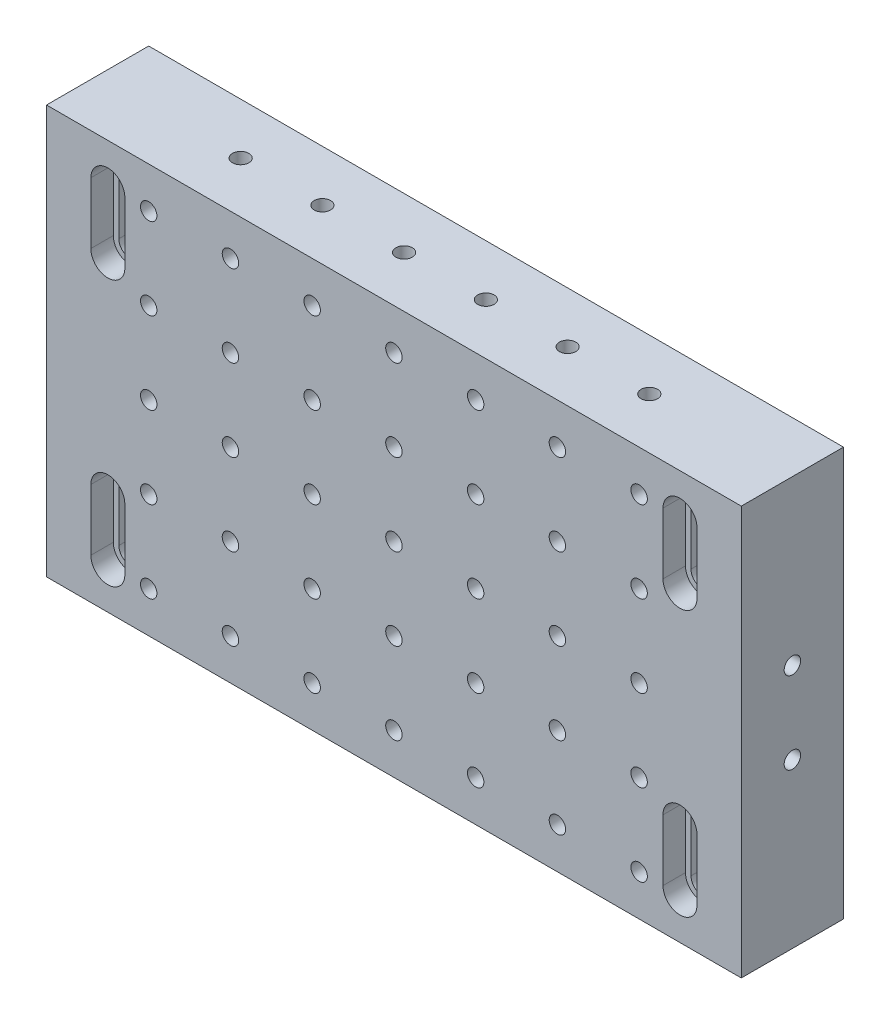
SolidWorks part; units mm, degrees
ref_plane "Front Plane" through (0, 0, 0) normal (0, 0, 1) x (1, 0, 0)
ref_plane "Top Plane" through (0, 0, 0) normal (0, 1, 0) x (1, 0, 0)
ref_plane "Right Plane" through (0, 0, 0) normal (1, 0, 0) x (0, 0, -1)
sketch "Sketch1" plane through (0, 0, 0) normal (0, 0, 1) x (1, 0, 0)
  line L1 (0, 0) -> (215.9, 0)
  line L2 (0, 0) -> (0, 127)
  line L3 (0, 127) -> (215.9, 127)
  line L4 (215.9, 0) -> (215.9, 127)
  dimension "D1" = 215.9
  dimension "D2" = 127
extrude "Boss-Extrude1" add sketch "Sketch1" along normal blind 31.75
sketch "Sketch2" plane through (0, 0, 0) normal (0, -1, 0) x (1, 0, 0)
  line L0 (13.7668, 31.75) -> (13.7668, 24.765)
  line L1 (0, 31.75) -> (215.9, 31.75) construction
  line L2 (13.7668, 24.765) -> (15.4813, 24.765)
  line L3 (15.4813, 24.765) -> (15.4813, 0)
  line L4 (0, 0) -> (215.9, 0) construction
  line L5 (15.4813, 0) -> (22.6187, 0)
  line L6 (22.6187, 0) -> (22.6187, 24.765)
  line L7 (22.6187, 24.765) -> (24.3332, 24.765)
  line L8 (24.3332, 24.765) -> (24.3332, 31.75)
  line L9 (24.3332, 31.75) -> (13.7668, 31.75)
  line L10 (19.05, 0) -> (19.05, 31.75) construction
extrude "Cut-Extrude1" cut sketch "Sketch2" against normal blind 19.05 from offset 12.7 offset against normal yes
sketch "Sketch4" plane through (0, 31.75, 0) normal (0, -1, 0) x (1, 0, 0)
  line L0 (19.05, 0) -> (19.05, 31.75)
  line L1 (15.4813, 0) -> (22.6187, 0) construction
  line L2 (24.3332, 31.75) -> (13.7668, 31.75) construction
  line L3 (19.05, 31.75) -> (13.7668, 31.75)
  line L4 (13.7668, 31.75) -> (13.7668, 24.765)
  line L5 (13.7668, 24.765) -> (15.4813, 24.765)
  line L6 (15.4813, 24.765) -> (15.4813, 0)
  line L7 (15.4813, 0) -> (19.05, 0)
revolve "Cut-Revolve3" cut sketch "Sketch4" angle 360 about L0
sketch "Sketch6" plane through (0, 12.7, 0) normal (0, 1, 0) x (1, 0, 0)
  line L0 (19.05, 0) -> (19.05, -31.75)
  line L1 (15.4813, 0) -> (22.6187, 0) construction
  line L2 (24.3332, -31.75) -> (13.7668, -31.75) construction
  line L3 (19.05, -31.75) -> (24.3332, -31.75)
  line L4 (24.3332, -31.75) -> (24.3332, -24.765)
  line L5 (24.3332, -24.765) -> (22.6187, -24.765)
  line L6 (22.6187, -24.765) -> (22.6187, 0)
  line L7 (22.6187, 0) -> (19.05, 0)
revolve "Cut-Revolve4" cut sketch "Sketch6" angle 360 about L0
pattern_linear "LPattern1" count 2 spacing 82.55 along (0, 1, 0) count 2 spacing 177.8 along (1, 0, 0) of "Cut-Extrude1", "Cut-Revolve3", "Cut-Revolve4"
hole_wizard "1/4-20 Tapped Hole1" positions "Sketch8" profile "Sketch7" tap size "1/4-20" standard "Ansi Inch" end condition through all
sketch "Sketch8" plane through (0, 0, 31.75) normal (0, 0, 1) x (1, 0, 0)
  line L1 (0, 0) -> (215.9, 0) construction
  line L2 (0, 127) -> (0, 0) construction
  point P0 (31.75, 12.7)
  dimension "D1" = 31.75
  dimension "D2" = 12.7
sketch "Sketch7" plane through (31.75, 12.7, 31.75) normal (1, 0, 0) x (0, -1, 0)
  line L0 (0, 0) -> (0, 31.75)
  line L1 (0, 31.75) -> (2.5527, 31.75)
  line L2 (2.5527, 31.75) -> (2.5527, 0)
  line L5 (2.5527, 0) -> (0, 0)
  line L11 (0, -6.35) -> (0, 107.95) construction
  dimension "Thru Tap Drill Dia." = 5.1054
  dimension "Thru Tap Drill Depth" = 31.75
cosmetic thread "Hole Thread10" parameters "D2"=6.35
hole_wizard "1/4-20 Tapped Hole3" positions "Sketch12" profile "Sketch14" tap size "1/4-20" standard "Ansi Inch"
sketch "Sketch12" plane through (215.9, -229.0211, 31.4791) normal (1, 0, 0) x (0, 0, -1)
  line L2 (-0.2709, 229.0211) -> (-0.2709, 356.0211) construction
  line L3 (-0.2709, 229.0211) -> (31.4791, 229.0211) construction
  point P0 (15.6041, 279.8211)
  dimension "D1" = 15.875
  dimension "D2" = 50.8
sketch "Sketch14" plane through (215.9, 50.8, 15.875) normal (0, 1, 0) x (0, 0, -1)
  line L0 (0, 0) -> (0, 33.2838)
  line L1 (0, 33.2838) -> (2.5527, 31.75)
  line L2 (2.5527, 31.75) -> (2.5527, 0)
  line L5 (2.5527, 0) -> (0, 0)
  line L10 (0, 33.2838) -> (-2.5527, 31.75) construction
  line L11 (0, -6.35) -> (0, 107.95) construction
  dimension "Tap Drill Dia." = 5.1054
  dimension "Tap Drill Depth" = 31.75
  dimension "Drill Angle" = 118
cosmetic thread "Hole Thread3" parameters "D1"=25.4, "D2"=6.35
hole_wizard "1/4-20 Tapped Hole5" positions "Sketch20" profile "Sketch22" tap size "1/4-20" standard "Ansi Inch"
sketch "Sketch20" plane through (169.6356, 127, -274.3412) normal (0, 1, 0) x (-1, 0, 0)
  line L2 (-46.2644, 306.0912) -> (169.6356, 306.0912) construction
  line L3 (-46.2644, 306.0912) -> (-46.2644, 274.3412) construction
  point P0 (-1.8144, 290.2162)
  dimension "D1" = 15.875
  dimension "D2" = 44.45
sketch "Sketch22" plane through (171.45, 127, 15.875) normal (1, 0, 0) x (0, 0, 1)
  line L0 (0, 0) -> (0, 33.2838)
  line L1 (0, 33.2838) -> (2.5527, 31.75)
  line L2 (2.5527, 31.75) -> (2.5527, 0)
  line L5 (2.5527, 0) -> (0, 0)
  line L10 (0, 33.2838) -> (-2.5527, 31.75) construction
  line L11 (0, -6.35) -> (0, 107.95) construction
  dimension "Tap Drill Dia." = 5.1054
  dimension "Tap Drill Depth" = 31.75
  dimension "Drill Angle" = 118
cosmetic thread "Hole Thread7" parameters "D1"=25.4, "D2"=6.35
pattern_linear "LPattern7" count 6 spacing 25.4 along (-1, 0, 0) of "1/4-20 Tapped Hole5"
ref_plane "centerplane1" through (107.95, 0, 0) normal (1, 0, 0) x (0, 0, -1)
ref_plane "centerplane2" through (0, 63.5, 0) normal (0, 1, 0) x (-1, 0, 0)
pattern_linear "LPattern10" count 7 spacing 25.4 along (1, 0, 0) count 5 spacing 25.4 along (0, 1, 0) of "1/4-20 Tapped Hole1"
mirror "Mirror1" about plane through (107.95, 0, 0) normal (1, 0, 0) of "1/4-20 Tapped Hole3"
mirror "Mirror2" about plane through (0, 63.5, 0) normal (0, 1, 0) of "Mirror1", "1/4-20 Tapped Hole3"
mirror "Mirror3" about plane through (0, 63.5, 0) normal (0, 1, 0) of "1/4-20 Tapped Hole5", "LPattern7"
